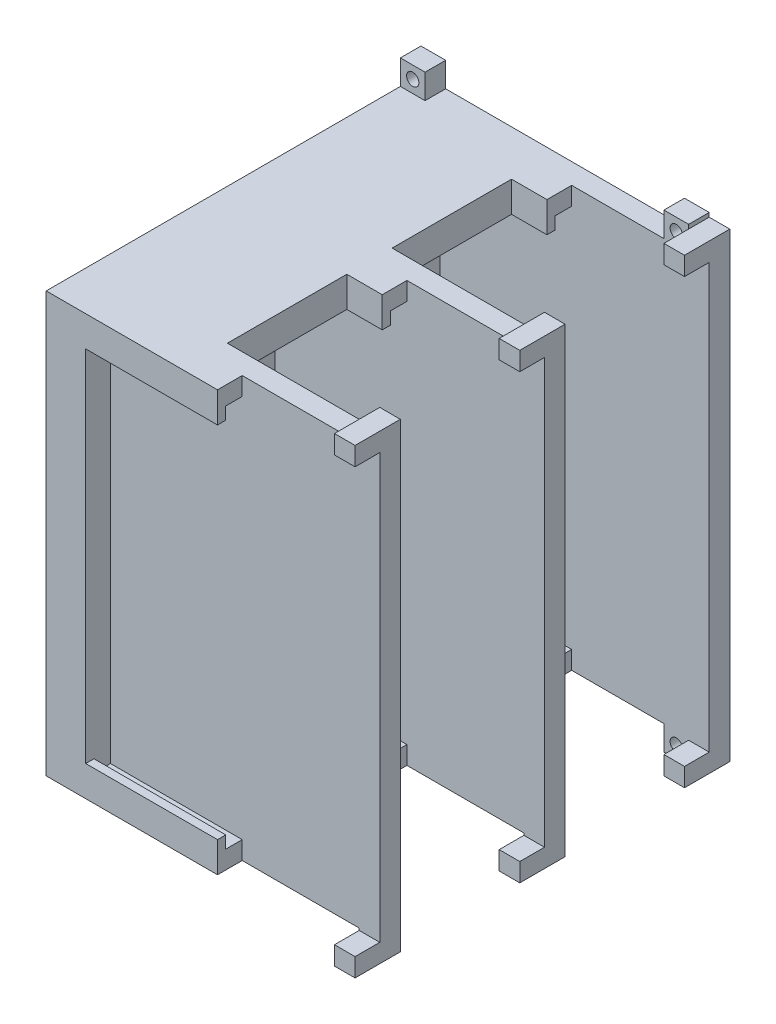
SolidWorks part; units mm, degrees
ref_plane "Front Plane" through (0, 0, 0) normal (1, 0, 0) x (0, 1, 0)
ref_plane "Top Plane" through (0, 0, 0) normal (0, 0, 1) x (0, 1, 0)
ref_plane "Right Plane" through (0, 0, 0) normal (0, 1, 0) x (-1, 0, 0)
sketch "Sketch1" plane through (0, 0, 0) normal (0, 0, 1) x (0, 1, 0)
  line L2 (-51, 5) -> (-51, 75)
  line L3 (-51, 75) -> (51, 75)
  line L4 (51, 5) -> (51, 75)
  line L5 (-56, 0) -> (-56, 5)
  line L6 (-56, 5) -> (-51, 5)
  line L7 (0, 75) -> (0, 0) construction
  line L9 (56, 0) -> (56, 5)
  line L10 (56, 5) -> (51, 5)
  line L11 (-56, 0) -> (56, 0)
  dimension "D1" = 102
  dimension "D2" = 5
  dimension "D3" = 5
  dimension "D4" = 75
extrude "Boss-Extrude1" add sketch "Sketch1" along normal blind 5
sketch "Sketch4" plane through (0, 0, 5) normal (0, 0, 1) x (1, 0, 0)
  line L0 (-75, 51) -> (-75, -51)
  line L1 (-5, 51.5) -> (0, 51.5)
  line L2 (-5, 51.5) -> (-5, 56)
  line L3 (-5, 56) -> (0, 56)
  line L4 (0, 51.5) -> (0, 56)
  line L9 (-75, 51) -> (-33.4, 51)
  line L11 (-65.4, 46.6) -> (-33.4, 46.6)
  line L12 (-33.4, 51) -> (-33.4, 46.6)
  line L13 (-75, -51) -> (-33.4, -51)
  line L15 (-65.4, -46.6) -> (-33.4, -46.6)
  line L16 (-33.4, -51) -> (-33.4, -46.6)
  line L17 (-65.4, 46.6) -> (-65.4, -46.6)
  line L18 (-5, 51) -> (-75, 51) construction
  line L19 (-5, 56) -> (-5, 51) construction
  line L20 (0, 0) -> (-65.4, 0) construction
  line L21 (-5, -56) -> (0, -56)
  line L22 (0, -51.5) -> (0, -56)
  line L23 (-5, -51.5) -> (0, -51.5)
  line L24 (-5, -51.5) -> (-5, -56)
  dimension "D1" = 4.4
  dimension "D2" = 32
  dimension "D3" = 4.4
  dimension "D4" = 9.6
  dimension "D5" = 0.5
extrude "Boss-Extrude2" add sketch "Sketch4" along normal blind 6
sketch "Sketch5" plane through (-65.4, 0, 0) normal (1, 0, 0) x (0, 1, 0)
  line L0 (0, 11) -> (0, 5) construction
  line L1 (-46.6, 11) -> (-43.6, 11)
  line L2 (-46.6, 11) -> (-46.6, 9)
  line L3 (-46.6, 9) -> (-43.6, 9)
  line L4 (-43.6, 11) -> (-43.6, 9)
  line L5 (-46.6, 11) -> (46.6, 11) construction
  line L6 (-46.6, 5) -> (46.6, 5) construction
  line L7 (46.6, 9) -> (43.6, 9)
  line L8 (43.6, 11) -> (43.6, 9)
  line L9 (46.6, 11) -> (43.6, 11)
  line L10 (46.6, 11) -> (46.6, 9)
  dimension "D1" = 3
  dimension "D2" = 2
extrude "Boss-Extrude3" add sketch "Sketch5" along normal up to surface (32 mm away) up to face at (-33.4, -48.8, 8)
sketch "Sketch6" plane through (0, 0, 0) normal (0, 0, -1) x (1, 0, 0)
  line L0 (-40, 51) -> (-40, -51) construction
  line L1 (-5, 51) -> (-11, 51)
  line L2 (-5, 51) -> (-5, 57)
  line L3 (-5, 57) -> (-11, 57)
  line L4 (-11, 51) -> (-11, 57)
  line L5 (-75, 51) -> (-5, 51) construction
  line L6 (-5, -51) -> (-75, -51) construction
  line L7 (-75, 0) -> (0, 0) construction
  line L8 (-75, -51) -> (-75, 51) construction
  line L9 (-75, 57) -> (-69, 57)
  line L10 (-69, 51) -> (-69, 57)
  line L11 (-75, 51) -> (-69, 51)
  line L12 (-75, 51) -> (-75, 57)
  line L13 (-5, -57) -> (-11, -57)
  line L14 (-11, -51) -> (-11, -57)
  line L15 (-5, -51) -> (-11, -51)
  line L16 (-5, -51) -> (-5, -57)
  line L17 (-75, -51) -> (-75, -57)
  line L18 (-75, -51) -> (-69, -51)
  line L19 (-69, -51) -> (-69, -57)
  line L20 (-75, -57) -> (-69, -57)
  dimension "D1" = 6
extrude "Boss-Extrude4" add sketch "Sketch6" against normal blind 5 separate body
sketch "Sketch7" plane through (0, 0, 5) normal (0, 0, 1) x (1, 0, 0)
  line L0 (-11, -54) -> (-5, -54) construction
  line L1 (-11, -57) -> (-11, -51) construction
  line L2 (-5, -51) -> (-5, -57) construction
  line L3 (0, 0) -> (-65.4, 0) construction
  line L4 (-65.4, -46.6) -> (-65.4, 46.6) construction
  line L5 (-75, -54) -> (-69, -54) construction
  line L6 (-75, -57) -> (-75, -51) construction
  line L7 (-69, -51) -> (-69, -57) construction
  circle A0 centre (-8, -54) radius 1.5
  circle A1 centre (-72, -54) radius 1.5
  circle A2 centre (-8, 54) radius 1.5
  circle A3 centre (-72, 54) radius 1.5
  dimension "D1" = 3
  dimension "D2" = 3
extrude "Cut-Extrude1" cut sketch "Sketch7" against normal through all
pattern_linear "LPattern1" count 3 spacing 40 along (0, 0, 1) of bodies 103
sketch "Sketch8" plane through (0, 0, 11) normal (0, 0, 1) x (1, 0, 0)
  line L0 (-75, 51) -> (-42, 51)
  line L1 (-33.4, 51) -> (-75, 51) construction
  line L2 (-42, 51) -> (-42, 43.6)
  line L3 (-33.4, 43.6) -> (-65.4, 43.6) construction
  line L4 (-42, 43.6) -> (-65.4, 43.6)
  line L5 (-65.4, -46.6) -> (-65.4, 46.6) construction
  line L6 (-65.4, 43.6) -> (-65.4, -43.6)
  line L7 (-33.4, -43.6) -> (-65.4, -43.6) construction
  line L8 (-65.4, -43.6) -> (-65.4, 43.6) construction
  line L9 (-65.4, -43.6) -> (-60, -43.6)
  line L10 (-60, -43.6) -> (-60, -51)
  line L11 (-75, -51) -> (-33.4, -51) construction
  line L12 (-60, -51) -> (-75, -51)
  line L13 (-75, -51) -> (-75, 51)
  dimension "D1" = 33
  dimension "D2" = 15
extrude "Boss-Extrude5" add sketch "Sketch8" along normal up to surface (29 mm away) up to face at (-21.25, 0, 40)
sketch "Sketch9" plane through (0, 0, 51) normal (0, 0, 1) x (1, 0, 0)
  line L0 (-75, 51) -> (-42, 51)
  line L1 (-33.4, 51) -> (-75, 51) construction
  line L2 (-42, 51) -> (-42, 43.6)
  line L3 (-33.4, 43.6) -> (-65.4, 43.6) construction
  line L4 (-42, 43.6) -> (-65.4, 43.6)
  line L5 (-65.4, 43.6) -> (-65.4, -43.6)
  line L6 (-65.4, -43.6) -> (-60, -43.6)
  line L7 (-60, -43.6) -> (-60, -51)
  line L8 (-75, -51) -> (-33.4, -51) construction
  line L9 (-60, -51) -> (-75, -51)
  line L10 (-75, -51) -> (-75, 51)
  dimension "D1" = 15
  dimension "D2" = 33
extrude "Boss-Extrude6" add sketch "Sketch9" along normal up to surface (29 mm away) up to face at (-21.25, 0, 80)
combine bodies "Combine1" operation type add bodies to combine 116 115 110 109 112 111
